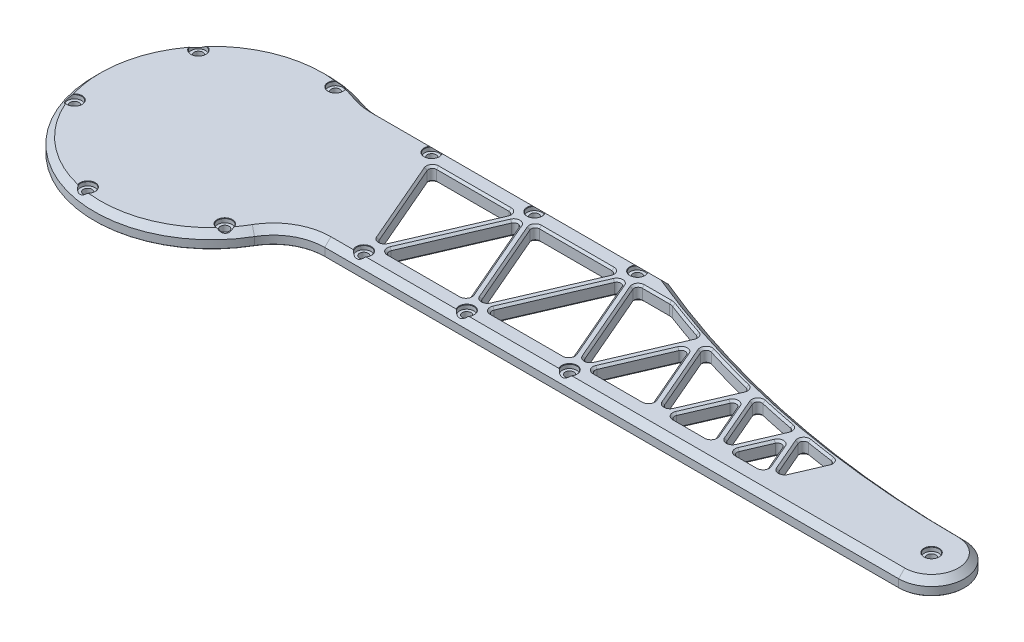
SolidWorks part; units mm, degrees
note: The reader was unsure of these and kept them because the rebuilt part matched: shared geometry of "스케치6<3>", "스케치7<3>".
material "6061-T6 (SS)"
ref_plane "정면" through (0, 0, 0) normal (0, 0, 1) x (1, 0, 0)
ref_plane "윗면" through (0, 0, 0) normal (0, 1, 0) x (1, 0, 0)
ref_plane "우측면" through (0, 0, 0) normal (1, 0, 0) x (0, 0, -1)
sketch "스케치1" plane through (0, 0, 0) normal (0, 1, 0) x (1, 0, 0)
  line L0 (0, 0) -> (350, 0) construction
  line L1 (0, 45) -> (0, 0) construction
  line L2 (0, 0) -> (38.9711, 22.5) construction
  line L3 (71.0141, -16) -> (350, -16)
  line L4 (350, -14) -> (71.0141, -14)
  line L5 (350, 32) -> (350, 40) construction
  line L6 (350, 16) -> (46.3141, 16) construction
  line L7 (350, 40) -> (40.6079, 40) construction
  line L8 (169.6004, 50) -> (28.1957, 50)
  line L9 (170, 52) -> (28.1957, 52)
  line L10 (85, -11) -> (185, -11) construction
  line L11 (0, 32) -> (350, 32) construction
  line L12 (0, 45) -> (0, 0) construction
  line L13 (0, 0) -> (-39.8343, 33.425) construction
  line L14 (-39.8343, 33.425) -> (0, 0) construction
  line L15 (0, 0) -> (-52, 0) construction
  line L16 (60, 47) -> (160, 47) construction
  line L17 (-39.8343, 33.425) -> (0, 0) construction
  line L18 (0, 0) -> (9.0297, 51.21) construction
  circle A18 centre (0, 0) radius 41
  circle A19 centre (350, 0) radius 6
  circle A25 centre (0, 0) radius 45
  circle A26 centre (0, 0) radius 49
  circle A28 centre (0, 45) radius 2.1
  circle A33 centre (0, 45) radius 3.5
  circle A34 centre (38.9711, 22.5) radius 2.1
  circle A36 centre (38.9711, 22.5) radius 3.5
  circle A37 centre (38.9711, -22.5) radius 2.1
  circle A38 centre (38.9711, -22.5) radius 3.5
  circle A40 centre (0, -45) radius 2.1
  circle A41 centre (0, -45) radius 3.5
  circle A42 centre (-38.9711, -22.5) radius 2.1
  circle A44 centre (-38.9711, -22.5) radius 3.5
  circle A45 centre (-38.9711, 22.5) radius 2.1
  circle A46 centre (-38.9711, 22.5) radius 3.5
  circle A48 centre (350, 0) radius 14
  arc A49 (322.2872, -16) -> (322.7607, 16.7934) centre (350, 0) ccw
  circle A50 centre (0, 0) radius 32
  arc A52 (350, -16) -> (342.254, -14) centre (350, 0) ccw
  arc A60 (170, 52) -> (350, 16) centre (350, 484) ccw
  arc A61 (169.6004, 50) -> (350, 14) centre (350, 484) ccw
  arc A75 (19.5995, 53.5244) -> (49.3634, -28.5) centre (0, 0) ccw
  arc A110 (71.0141, -16) -> (49.3634, -28.5) centre (71.0141, -41) ccw
  arc A111 (71.0141, -14) -> (47.6314, -27.5) centre (71.0141, -41) ccw
  circle A114 centre (0, 0) radius 55
  circle A130 centre (0, 0) radius 52
  circle A131 centre (60, 47) radius 2.1
  circle A142 centre (-39.8343, 33.425) radius 2.1
  circle A143 centre (9.0297, 51.21) radius 2.1
  circle A145 centre (39.8343, -33.425) radius 2.1
  circle A146 centre (-9.0297, -51.21) radius 2.1
  arc A147 (19.5995, 53.5244) -> (28.1957, 52) centre (28.1957, 77) ccw
  arc A148 (18.9118, 51.6463) -> (28.1957, 50) centre (28.1957, 77) ccw
  arc A149 (53.0537, -20.84) -> (27.3679, 50) centre (0, 0) ccw
  circle A152 centre (85, -11) radius 2.1
  circle A161 centre (135, -11) radius 2.1
  circle A165 centre (185, -11) radius 2.1
  circle A168 centre (110, 47) radius 2.1
  circle A172 centre (235, -11) radius 2.1 [skipped]
  circle A177 centre (160, 47) radius 2.1
  circle A180 centre (0, 0) radius 57
  circle A181 centre (-48.864, -17.785) radius 2.1
  circle A182 centre (48.864, 17.785) radius 2.1 [skipped]
  point P29 (0, 0)
  point P57 (-0.5, 0.2887)
  point P59 (0, 0)
  point P73 (0, 0)
  point P120 (0, 0)
  point P168 (0, 0)
  point P170 (0, 0)
  point P171 (0, 0)
  dimension "D2" = 82
  dimension "D3" = 90
  dimension "D4" = 98
  dimension "D7" = 7
  dimension "D8" = 60
  dimension "D10" = 28
  dimension "D11" = 64
  dimension "D12" = 64
  dimension "D13" = 32
  dimension "D14" = 60
  dimension "D19" = 50
  dimension "D21" = 50
  dimension "D17" = 180
  dimension "D20" = 3
  dimension "D22" = 8
  dimension "D23" = 2
  dimension "D25" = 50
  dimension "D26" = 4.2
  dimension "D28" = 85
  dimension "D32" = 3
  dimension "D33" = 50
  dimension "D35" = 4
  dimension "D5" = 114
  dimension "D6" = 4.2
  dimension "D9" = 12
  dimension "D18" = 6
  dimension "D16" = 104
  dimension "D27" = 4.2
  dimension "D37" = 25
  dimension "D15" = 4.2
  dimension "D1" = 350
  dimension "D34" = 6
  dimension "D38" = 50
  dimension "D24" = 10
  dimension "D30" = 3
sketch "스케치2" plane through (0, 0, 0) normal (0, 1, 0) x (1, 0, 0)
  circle A10 centre (350, 0) radius 6.25
  circle A11 centre (382.6753, 12.5429) radius 10
  arc A12 (390.9123, -1.174) -> (378.5037, 27.9895) centre (382.6753, 12.5429) ccw
  arc A13 (231.9844, -40.1605) -> (80.8156, -91.5048) centre (227.4834, -275.1173) ccw
  arc A14 (357.0381, -19.254) -> (358.9138, -18.4606) centre (350, 0) ccw
  arc A15 (358.9138, -18.4606) -> (390.9123, -1.174) centre (184.9867, 341.7468) ccw
  arc A16 (231.9844, -40.1605) -> (357.0381, -19.254) centre (238.5923, 304.7763) ccw
  arc A17 (378.5037, 27.9895) -> (343.7427, 16.8774) centre (482.7931, -358.1759) ccw
  arc A18 (233.0814, -9.5331) -> (343.3893, 16.7421) centre (196.4849, 388.7893) ccw
  arc A19 (233.0814, -9.5331) -> (41.3157, -82.3545) centre (261.5552, -373.4208) ccw
sketch "스케치3" plane through (0, 0, 0) normal (0, 1, 0) x (1, 0, 0)
  line L0 (350, -2.1721) -> (350, 87.1857) construction
  line L1 (350, 32) -> (0, 32) construction
  line L2 (350, 36) -> (-50.8808, 36) construction
  line L3 (350, 28) -> (-10.04, 28) construction
  circle A0 centre (356.8277, -1.9267) radius 6.25
  circle A1 centre (350, 32) radius 10
  arc A2 (365.7576, 37.7743) -> (333.8887, 36.6981) centre (350, 32) ccw
  arc A3 (345.2, -124.5693) -> (338.96, -284.0977) centre (562.9381, -212.9724) ccw
  arc A4 (377.1409, -4.6879) -> (376.6334, 3.3632) centre (356.8277, -1.9267) ccw
  arc A5 (376.6334, 3.3632) -> (365.7576, 37.7743) centre (-9.8202, -99.853) ccw
  arc A6 (345.2, -124.5693) -> (377.1409, -4.6879) centre (-114.7569, 62.1762) ccw
  arc A7 (333.8887, 36.6981) -> (325.3353, 1.5106) centre (717.8951, -75.28) ccw
  arc A8 (317, -112.5693) -> (332.0008, -0.1718) centre (-67.981, -3.9891) ccw
  arc A9 (317, -112.5693) -> (316.262, -317.6949) centre (666.9225, -216.3924) ccw
  dimension "D1" = 4
  dimension "D2" = 4
extrude "보스-돌출1" add sketch "스케치1" along normal blind 7 contours A50 | A18 A50 | A46 A25 A44 A41 A38 A36 A33 A18 | A26 A46 A25 A33 A36 A38 A41 A44 | A181 A130 A146 A145 A143 A142 A26 | A114 A181 A130 A142 A143 A145 A146 | A75 A180 A111 A114 A148 | A25 A33 A28 | A25 A28 | A25 A28 | A25 A33 A28 | A25 A46 A45 | A25 A45 | A25 A45 | A25 A46 A45 | A25 A44 A42 | A25 A42 | A25 A42 | A25 A44 A42 | A25 A41 A40 | A25 A40 | A25 A40 | A25 A41 A40 | A25 A38 A37 | A25 A37 | A25 A37 | A25 A38 A37 | A25 A36 A34 | A25 A36 A34 | A25 A34 | A25 A34 | A149 A180 A148 A114 A111 | A180 A148 L8 A61 A52 A60 L9 A147 | A180 A149 A111 L4 A52 A61 L8 A148 A177 A168 A165 A161 A152 A131 | A180 A110 L3 A52 A61 A48 L4 A111 | A61 A52 L4 A48 | A48 A19
sketch "스케치4" plane through (0, 0, 0) normal (0, -1, 0) x (1, 0, 0)
  circle A0 centre (350, 0) radius 6
  circle A1 centre (350, 0) radius 8
  dimension "D1" = 12
  dimension "D2" = 16
extrude "보스-돌출2" add sketch "스케치4" along normal blind 1
sketch "스케치5" plane through (0, 7, 0) normal (0, 1, 0) x (1, 0, 0)
  circle A0 centre (9.0297, 51.21) radius 3.5
  circle A1 centre (60, 47) radius 3.5
  circle A2 centre (-39.8343, 33.425) radius 3.5
  circle A3 centre (-48.864, -17.785) radius 3.5
  circle A4 centre (-9.0297, -51.21) radius 3.5
  circle A5 centre (39.8343, -33.425) radius 3.5
  circle A6 centre (85, -11) radius 3.5
  circle A7 centre (110, 47) radius 3.5
  circle A8 centre (160, 47) radius 3.5
  circle A9 centre (135, -11) radius 3.5
  circle A10 centre (185, -11) radius 3.5
  dimension "D1" = 7
extrude "컷-돌출1" cut sketch "스케치5" against normal blind 2
sketch "스케치6" plane through (0, 0, 0) normal (0, -1, 0) x (1, 0, 0)
  line L0 (60, -47) -> (85, 11) construction
  line L1 (85, 11) -> (110, -47) construction
  line L2 (110, -47) -> (135, 11) construction
  line L3 (135, 11) -> (160, -47) construction
  line L4 (160, -47) -> (185, 11) construction
  line L5 (185, 11) -> (204.3845, -33.9721) construction
  line L6 (204.3845, -33.9721) -> (223.769, 11) construction
  line L7 (223.769, 11) -> (238.9504, -24.2207) construction
  line L8 (238.9504, -24.2207) -> (254.1317, 11) construction
  line L9 (254.1317, 11) -> (266.7938, -18.376) construction
  line L10 (266.7938, -18.376) -> (279.4558, 11) construction
  line L11 (279.4558, 11) -> (290.5551, -14.7503) construction
  line L12 (67.373, -42) -> (102.627, -42)
  line L13 (83.1634, 1.6863) -> (65.5364, -39.2083)
  line L14 (86.8366, 1.6863) -> (104.4636, -39.2083)
  line L15 (60, -47) -> (160, -47) construction
  line L16 (90.5364, 3.2083) -> (108.1634, -37.6863)
  line L17 (111.8366, -37.6863) -> (129.4636, 3.2083)
  line L18 (92.373, 6) -> (127.627, 6)
  line L19 (85, 11) -> (185, 11) construction
  line L20 (133.1634, 1.6863) -> (115.5364, -39.2083)
  line L21 (117.373, -42) -> (152.627, -42)
  line L22 (136.8366, 1.6863) -> (154.4636, -39.2083)
  line L23 (140.5364, 3.2083) -> (158.1634, -37.6863)
  line L24 (142.373, 6) -> (177.627, 6)
  line L25 (179.4636, 3.2083) -> (161.8366, -37.6863)
  line L26 (152.627, -42) -> (180.6631, -42) construction
  line L27 (183.1634, 1.6863) -> (165.5364, -39.2083)
  line L28 (186.8366, 1.6863) -> (201.6108, -32.5897)
  line L30 (180.6631, -42) -> (167.373, -42)
  line L31 (192.373, 6) -> (216.396, 6)
  line L32 (190.5364, 3.2083) -> (202.5479, -24.6584)
  line L33 (218.2327, 3.2083) -> (206.2212, -24.6584)
  line L34 (221.9324, 1.6863) -> (208.6351, -29.1633)
  line L35 (225.6057, 1.6863) -> (236.0469, -22.5374)
  line L36 (231.142, 6) -> (246.7587, 6)
  line L37 (229.3054, 3.2083) -> (237.1137, -14.907)
  line L38 (248.5954, 3.2083) -> (240.787, -14.907)
  line L39 (252.2951, 1.6863) -> (242.9438, -20.0088)
  line L40 (255.9684, 1.6863) -> (263.782, -16.4414)
  line L41 (261.5047, 6) -> (272.0828, 6)
  line L42 (259.6681, 3.2083) -> (264.9571, -9.0623)
  line L43 (273.9195, 3.2083) -> (268.6304, -9.0623)
  line L44 (277.6192, 1.6863) -> (270.6067, -14.5827)
  line L45 (281.2925, 1.6863) -> (287.4473, -12.5928)
  circle A0 centre (350, -484) radius 473
  arc A1 (350, -14) -> (169.6004, -50) centre (350, -484) ccw construction
  arc A2 (350, -16) -> (170, -52) centre (350, -484) ccw construction
  arc A3 (102.627, -42) -> (104.4636, -39.2083) centre (102.627, -40) ccw
  arc A4 (67.373, -42) -> (65.5364, -39.2083) centre (67.373, -40) cw
  arc A5 (86.8366, 1.6863) -> (83.1634, 1.6863) centre (85, 0.8946) ccw
  arc A6 (111.8366, -37.6863) -> (108.1634, -37.6863) centre (110, -36.8946) cw
  arc A7 (129.4636, 3.2083) -> (127.627, 6) centre (127.627, 4) ccw
  arc A8 (90.5364, 3.2083) -> (92.373, 6) centre (92.373, 4) cw
  arc A9 (154.4636, -39.2083) -> (152.627, -42) centre (152.627, -40) cw
  arc A10 (117.373, -42) -> (115.5364, -39.2083) centre (117.373, -40) cw
  arc A11 (136.8366, 1.6863) -> (133.1634, 1.6863) centre (135, 0.8946) ccw
  arc A12 (161.8366, -37.6863) -> (158.1634, -37.6863) centre (160, -36.8946) cw
  arc A13 (179.4636, 3.2083) -> (177.627, 6) centre (177.627, 4) ccw
  arc A14 (140.5364, 3.2083) -> (142.373, 6) centre (142.373, 4) cw
  arc A15 (167.373, -42) -> (165.5364, -39.2083) centre (167.373, -40) cw
  arc A16 (186.8366, 1.6863) -> (183.1634, 1.6863) centre (185, 0.8946) ccw
  arc A17 (200.4067, -35.2787) -> (201.6108, -32.5897) centre (199.7741, -33.3813) ccw
  arc A18 (206.2212, -24.6584) -> (202.5479, -24.6584) centre (204.3845, -23.8667) cw
  arc A19 (218.2327, 3.2083) -> (216.396, 6) centre (216.396, 4) ccw
  arc A20 (190.5364, 3.2083) -> (192.373, 6) centre (192.373, 4) cw
  arc A21 (225.6057, 1.6863) -> (221.9324, 1.6863) centre (223.769, 0.8946) ccw
  arc A22 (208.6351, -29.1633) -> (211.0593, -31.8668) centre (210.4718, -29.955) ccw
  arc A23 (234.6978, -25.2687) -> (236.0469, -22.5374) centre (234.2103, -23.329) ccw
  arc A24 (240.787, -14.907) -> (237.1137, -14.907) centre (238.9504, -14.1154) cw
  arc A25 (248.5954, 3.2083) -> (246.7587, 6) centre (246.7587, 4) ccw
  arc A26 (229.3054, 3.2083) -> (231.142, 6) centre (231.142, 4) cw
  arc A27 (255.9684, 1.6863) -> (252.2951, 1.6863) centre (254.1317, 0.8946) ccw
  arc A28 (242.9438, -20.0088) -> (245.2234, -22.7507) centre (244.7804, -20.8004) ccw
  arc A29 (262.3161, -19.1984) -> (263.782, -16.4414) centre (261.9454, -17.2331) ccw
  arc A30 (268.6304, -9.0623) -> (264.9571, -9.0623) centre (266.7938, -8.2706) cw
  arc A31 (273.9195, 3.2083) -> (272.0828, 6) centre (272.0828, 4) ccw
  arc A32 (259.6681, 3.2083) -> (261.5047, 6) centre (261.5047, 4) cw
  arc A33 (281.2925, 1.6863) -> (277.6192, 1.6863) centre (279.4558, 0.8946) ccw
  arc A34 (270.6067, -14.5827) -> (272.7699, -17.3475) centre (272.4433, -15.3744) ccw
  arc A35 (285.8817, -15.366) -> (287.4473, -12.5928) centre (285.6106, -13.3844) ccw
  circle A36 centre (0, 0) radius 47.5
  arc A37 (180.6631, -42) -> (182.4344, -41.6757) centre (180.6631, -37) ccw
  point P119 (273.1248, -3.688)
  dimension "D1" = 5
  dimension "D5" = 2
  dimension "D9" = 2
  dimension "D12" = 2
  dimension "D15" = 2
  dimension "D18" = 2
  dimension "D19" = 4
  dimension "D22" = 2
  dimension "D25" = 2
  dimension "D26" = 4
  dimension "D29" = 2
  dimension "D32" = 2
  dimension "D33" = 4
  dimension "D36" = 2
  dimension "D39" = 2
  dimension "D40" = 4
  dimension "D41" = 95
  dimension "D42" = 10
  dimension "D2" = 5
  dimension "D3" = 2
  dimension "D4" = 2
  dimension "D6" = 5
  dimension "D7" = 2
  dimension "D8" = 2
  dimension "D10" = 2
  dimension "D11" = 2
  dimension "D13" = 2
  dimension "D14" = 2
  dimension "D16" = 2
  dimension "D17" = 2
  dimension "D20" = 2
  dimension "D21" = 2
  dimension "D23" = 2
  dimension "D24" = 2
  dimension "D27" = 2
  dimension "D28" = 2
  dimension "D30" = 2
  dimension "D31" = 2
  dimension "D34" = 2
  dimension "D35" = 2
  dimension "D37" = 2
  dimension "D38" = 2
extrude "컷-돌출2" cut sketch "스케치6" against normal blind 7 contours L14 A5 L13 A4 L12 A3 | A8 L16 A6 L17 A7 L18 | L22 A11 L20 A10 L21 A9 | A14 L23 A12 L25 A13 L24 | L30 A37 A0 A17 L28 A16 L27 A15 | A20 L32 A18 L33 A19 L31 | A0 A23 L35 A21 L34 A22 | A26 L37 A24 L38 A25 L36 | A0 A29 L40 A27 L39 A28 | A32 L42 A30 L43 A31 L41 | A0 A35 L45 A33 L44 A34
extrude "컷-돌출3" cut sketch "스케치6<3>" against normal blind 5 contours A36
sketch "스케치6<3>" plane through (0, 0, 0) normal (0, -1, 0) x (1, 0, 0) same geometry as "스케치6"
sketch "스케치7" plane through (0, 7, 0) normal (0, 1, 0) x (1, 0, 0)
  circle A0 centre (350, 0) radius 3.5
  circle A1 centre (350, 0) radius 6
  circle A2 centre (350, 0) radius 2.1
  dimension "D1" = 12
  dimension "D2" = 7
  dimension "D3" = 4.2
extrude "보스-돌출3" add sketch "스케치7" against normal blind 7
extrude "보스-돌출4" add sketch "스케치7<3>" against normal blind 5 from offset 2 contours A0 A2 offset against normal yes
sketch "스케치7<3>" plane through (0, 7, 0) normal (0, 1, 0) x (1, 0, 0) same geometry as "스케치7"
chamfer "모따기2" distance 3 angle 45 7 edges at (366, 7, 0) (258.2176, 7, -25.0882) (210.507, 7, 16) (99.0979, 7, -52) (58.5141, 7, 19.3494) (23.8306, 7, -52.384) (-53.5814, 7, 19.443)
chamfer "모따기3" distance 1 angle 45 138 edges at (0, 5, -47.5) (0, 0, -47.5) (95.6501, 0, -18.761) (95.6501, 7, -18.761) (104.2978, 0, -41.0992) (104.2978, 7, -41.0992) (85, 0, -42) (85, 7, -42) (85, 0, 2.8946) (85, 7, 2.8946) (74.3499, 0, -18.761) (74.3499, 7, -18.761) (65.7022, 0, -41.0992) (65.7022, 7, -41.0992) (90.7022, 0, 5.0992) (90.7022, 7, 5.0992) (99.3499, 0, -17.239) (99.3499, 7, -17.239) (110, 0, -38.8946) (110, 7, -38.8946) (110, 0, 6) (110, 7, 6) (129.2978, 0, 5.0992) (129.2978, 7, 5.0992) (120.6501, 0, -17.239) (120.6501, 7, -17.239) (135, 0, 2.8946) (135, 7, 2.8946) (145.6501, 0, -18.761) (145.6501, 7, -18.761) (154.2978, 0, -41.0992) (154.2978, 7, -41.0992) (135, 0, -42) (135, 7, -42) (115.7022, 0, -41.0992) (115.7022, 7, -41.0992) (124.3499, 0, -18.761) (124.3499, 7, -18.761) (160, 0, -38.8946) (160, 7, -38.8946) (149.3499, 0, -17.239) (149.3499, 7, -17.239) (140.7022, 0, 5.0992) (140.7022, 7, 5.0992) (160, 0, 6) (160, 7, 6) (179.2978, 0, 5.0992) (179.2978, 7, 5.0992) (170.6501, 0, -17.239) (170.6501, 7, -17.239) (185, 0, 2.8946) (185, 7, 2.8946) (194.2237, 0, -15.4517) (194.2237, 7, -15.4517) (201.5995, 0, -34.1987) (201.5995, 7, -34.1987) (191.3883, 0, -38.3866) (191.3883, 7, -38.3866) (181.5634, 0, -41.9183) (181.5634, 7, -41.9183) (174.018, 0, -42) (174.018, 7, -42) (174.3499, 0, -18.761) (174.3499, 7, -18.761) (165.7022, 0, -41.0992) (165.7022, 7, -41.0992) (204.3845, 0, 6) (204.3845, 7, 6) (190.7022, 0, 5.0992) (190.7022, 7, 5.0992) (218.0669, 0, 5.0992) (218.0669, 7, 5.0992) (212.2269, 0, -10.725) (212.2269, 7, -10.725) (204.3845, 0, -25.8667) (204.3845, 7, -25.8667) (196.5421, 0, -10.725) (196.5421, 7, -10.725) (238.9504, 0, 6) (238.9504, 7, 6) (248.4296, 0, 5.0992) (248.4296, 7, 5.0992) (244.6912, 0, -5.8493) (244.6912, 7, -5.8493) (238.9504, 0, -16.1154) (238.9504, 7, -16.1154) (233.2096, 0, -5.8493) (233.2096, 7, -5.8493) (229.4712, 0, 5.0992) (229.4712, 7, 5.0992) (266.7938, 0, 6) (266.7938, 7, 6) (273.7537, 0, 5.0992) (273.7537, 7, 5.0992) (271.275, 0, -2.927) (271.275, 7, -2.927) (266.7938, 0, -10.2706) (266.7938, 7, -10.2706) (262.3126, 0, -2.927) (262.3126, 7, -2.927) (259.8339, 0, 5.0992) (259.8339, 7, 5.0992) (270.8682, 0, -16.6068) (270.8682, 7, -16.6068) (274.1129, 0, -6.4482) (274.1129, 7, -6.4482) (279.4558, 0, 2.8946) (279.4558, 7, 2.8946) (284.3699, 0, -5.4532) (284.3699, 7, -5.4532) (287.3523, 0, -14.3676) (287.3523, 7, -14.3676) (279.3189, 0, -16.3108) (279.3189, 7, -16.3108) (230.8263, 0, -10.4255) (230.8263, 7, -10.4255) (223.769, 0, 2.8946) (223.769, 7, 2.8946) (215.2838, 0, -13.7385) (215.2838, 7, -13.7385) (208.9827, 0, -31.2902) (208.9827, 7, -31.2902) (222.8357, 0, -28.4144) (222.8357, 7, -28.4144) (236.0034, 0, -24.2148) (236.0034, 7, -24.2148) (247.6194, 0, -9.1612) (247.6194, 7, -9.1612) (254.1317, 0, 2.8946) (254.1317, 7, 2.8946) (259.8752, 0, -7.3775) (259.8752, 7, -7.3775) (263.7113, 0, -18.172) (263.7113, 7, -18.172) (243.2425, 0, -22.079) (243.2425, 7, -22.079) (253.7534, 0, -20.8957) (253.7534, 7, -20.8957)
chamfer "모따기4" distance 0.2 angle 45 21 edges at (350, 7, 3.5) (185, 7, 7.5) (135, 7, 7.5) (85, 7, 7.5) (37.1532, 7, 31.1752) (-8.4219, 7, 47.7632) (-45.5751, 7, 16.588) (-37.1532, 7, -31.1752) (8.4219, 7, -47.7632) (60, 7, -43.5) (110, 7, -43.5) (160, 7, -43.5) (58.5141, 0, 19.3494) (-53.5814, 0, 19.443) (23.8306, 0, -52.384) (99.0979, 0, -52) (210.507, 0, 16) (258.2176, 0, -25.0882) (366, 0, 0) (350, -1, -6) (350, -1, -8)
